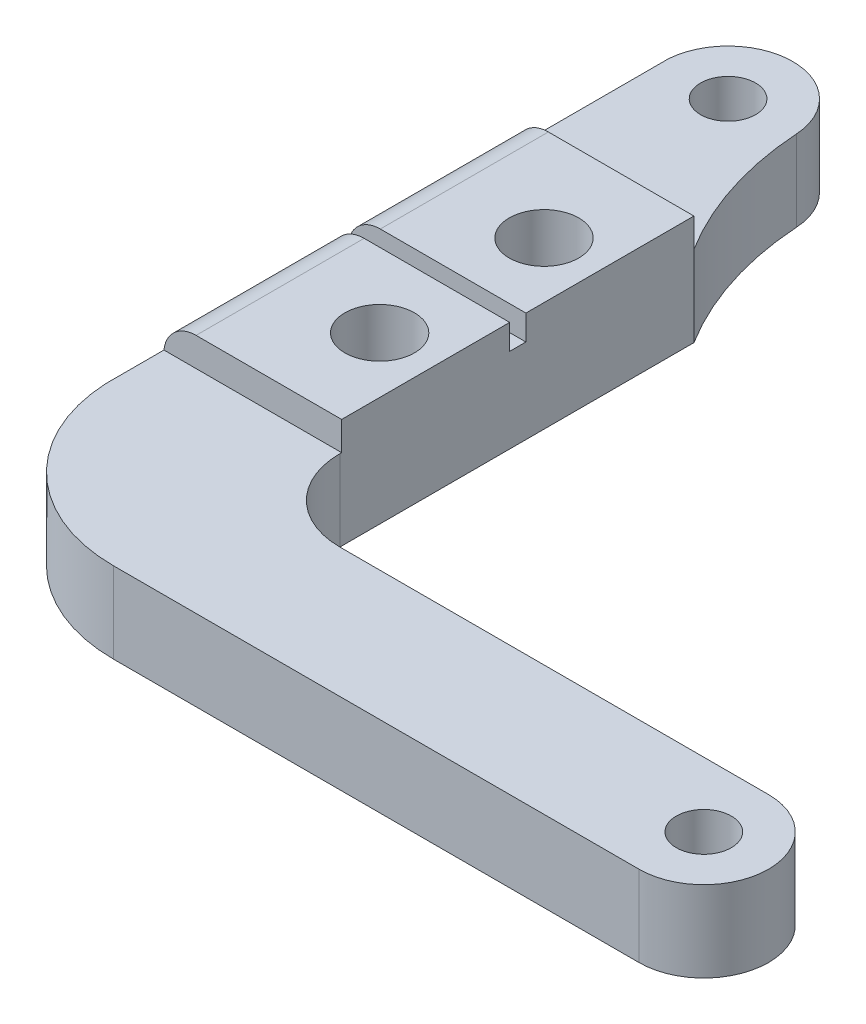
SolidWorks part; units mm, degrees
ref_plane "Plan de face" through (0, 0, 0) normal (0, 0, 1) x (1, 0, 0)
ref_plane "Plan de dessus" through (0, 0, 0) normal (0, 1, 0) x (1, 0, 0)
ref_plane "Plan de droite" through (0, 0, 0) normal (1, 0, 0) x (0, 0, -1)
sketch "Esquisse2" plane through (0, 0, 0) normal (0, 1, 0) x (1, 0, 0)
  line L0 (4, -36) -> (38.5, -36)
  line L1 (4, 0) -> (4, -9.11)
  line L2 (-4, -44) -> (38.5, -44)
  line L3 (-4, -44) -> (-4, 0)
  line L4 (4, -30.89) -> (4, -36)
  line L5 (4, -9.11) -> (7, -9.11)
  line L7 (4, -30.89) -> (7, -30.89)
  line L8 (7, -9.11) -> (7, -30.89)
  arc A0 (4, 0) -> (-4, 0) centre (0, 0) ccw
  arc A1 (38.5, -44) -> (38.5, -36) centre (38.5, -40) ccw
  dimension "D1" = 8
  dimension "D2" = 8
  dimension "D3" = 38.5
  dimension "D4" = 44
  dimension "D5" = 42.5
  dimension "D6" = 34.5
  dimension "D7" = 36
  dimension "D8" = 5.11
  dimension "2" = 3
  dimension "D9" = 21.78
  dimension "D10" = 40
extrude "Boss.-Extru.1" add sketch "Esquisse2" along normal blind 5
hole_wizard "Dégagement M31" positions "Esquisse3" profile "Esquisse4" size "M3" standard "Ansi Metric" slot yes end condition through all
sketch "Esquisse3" plane through (0, 5, 0) normal (0, 1, 0) x (1, 0, 0)
  point P0 (0, 0)
  point P3 (38.5, -40)
sketch "Esquisse4" plane through (0, 5, 0) normal (1, 0, 0) x (0, 0, 1)
  line L0 (0, 0) -> (0, 5)
  line L1 (0, 5) -> (1.7, 5)
  line L2 (1.7, 5) -> (1.7, 0)
  line L5 (1.7, 0) -> (0, 0)
  line L11 (0, -6.35) -> (0, 107.95) construction
  dimension "Diamètre du perçage jusqu'au prochain" = 3.4
  dimension "Profondeur du perçage jusqu'au prochain" = 5
sketch "Esquisse5" plane through (0, 5, 0) normal (0, 1, 0) x (1, 0, 0)
  line L0 (-4, 0) -> (-4, -44) construction
  line L1 (7, -9.11) -> (-4, -9.11)
  line L2 (7, -9.11) -> (7, -30.89)
  line L3 (7, -30.89) -> (-4, -30.89)
  line L4 (-4, -9.11) -> (-4, -30.89)
  line L5 (4, -30.89) -> (7, -30.89) construction
extrude "Boss.-Extru.2" add sketch "Esquisse5" along normal blind 1.78
sketch "Esquisse6" plane through (-4, 0, 0) normal (-1, 0, 0) x (0, 0, 1)
  line L0 (9.11, 6.78) -> (30.89, 6.78) construction
  line L1 (19.5, 6.78) -> (20.5, 6.78)
  line L2 (19.5, 6.78) -> (19.5, 5.23)
  line L3 (19.5, 5.23) -> (20.5, 5.23)
  line L4 (20.5, 6.78) -> (20.5, 5.23)
  point P6 (20, 6.78)
  point P7 (20, 6.78)
  dimension "D1" = 1.55
  dimension "D2" = 1
extrude "Enlèv. mat.-Extru.1" cut sketch "Esquisse6" against normal through all
hole_wizard "Dégagement M42" positions "Esquisse7" profile "Esquisse8" size "M4" standard "Ansi Metric" slot yes end condition through all
sketch "Esquisse7" plane through (0, 6.78, 0) normal (0, 1, 0) x (1, 0, 0)
  circle A0 centre (38.5, -40) radius 1.7 construction
  point P0 (3.54, -25.08)
  point P2 (3.54, -14.92)
  dimension "D1" = 34.96
  dimension "D2" = 14.92
  dimension "D3" = 10.16
sketch "Esquisse8" plane through (3.54, 6.78, 25.08) normal (1, 0, 0) x (0, 0, 1)
  line L0 (0, 0) -> (0, 6.78)
  line L1 (0, 6.78) -> (2.15, 6.78)
  line L2 (2.15, 6.78) -> (2.15, 0)
  line L5 (2.15, 0) -> (0, 0)
  line L11 (0, -6.35) -> (0, 107.95) construction
  dimension "Diamètre du perçage jusqu'au prochain" = 4.3
  dimension "Profondeur du perçage jusqu'au prochain" = 6.78
sketch "Esquisse9" plane through (4, 0, 0) normal (1, 0, 0) x (0, 0, -1)
  line L1 (-36, 5) -> (-30.89, 5)
  line L2 (-36, 5) -> (-36, 0)
  line L3 (-36, 0) -> (-30.89, 0)
  line L4 (-30.89, 5) -> (-30.89, 0)
extrude "Boss.-Extru.3" add sketch "Esquisse9" along normal blind 3
fillet "Congé2" radius 5 1 edges at (7, 2.5, 36)
fillet "Congé3" radius 10 1 edges at (-4, 2.5, 44)
fillet "Congé4" radius 2 1 edges at (-4, 6.78, 14.305)
fillet "Congé5" radius 20 1 edges at (4, 2.5, 9.11)
